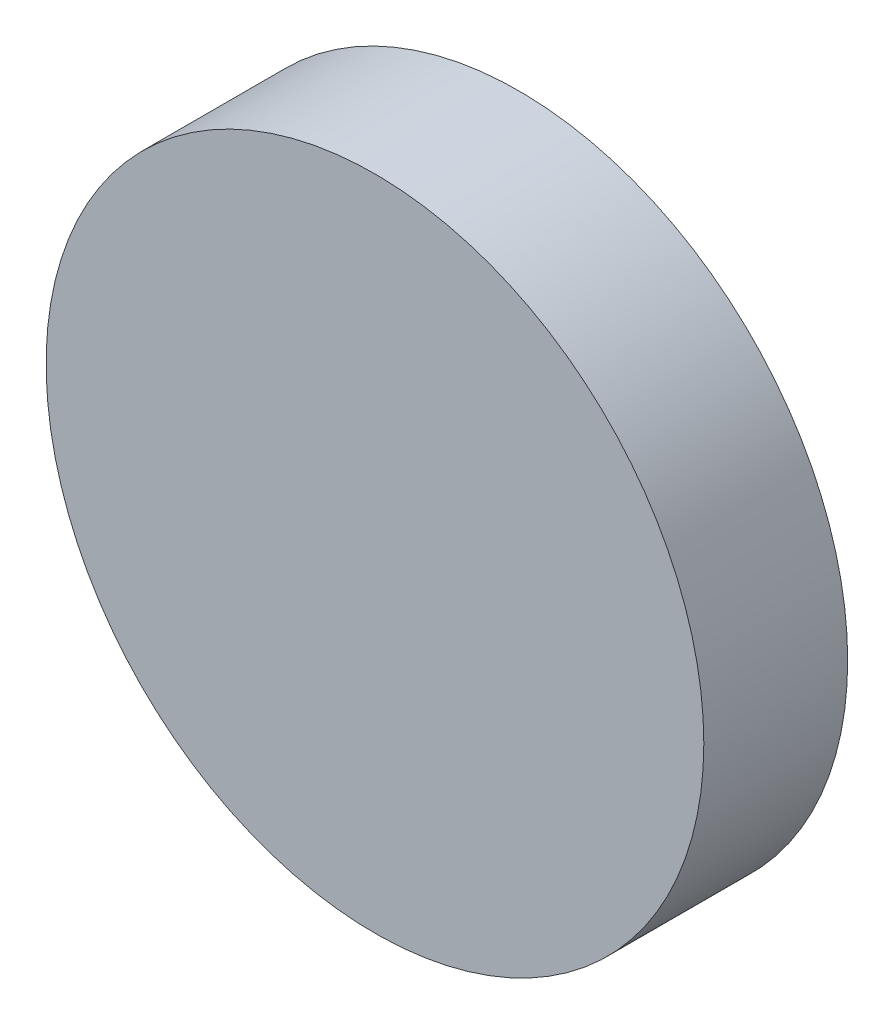
SolidWorks part; units mm, degrees
ref_plane "Alzado" through (0, 0, 0) normal (0, 0, 1) x (1, 0, 0)
ref_plane "Planta" through (0, 0, 0) normal (0, 1, 0) x (1, 0, 0)
ref_plane "Vista lateral" through (0, 0, 0) normal (1, 0, 0) x (0, 0, -1)
sketch "Croquis2" plane through (0, 0, 34) normal (0, 0, 1) x (1, 0, 0)
  circle A3 centre (13.5413, 6.6268) radius 40
  circle A6 centre (13.5413, 6.6268) radius 37.5
extrude "Saliente-Extruir1" add sketch "Croquis2" along normal blind 12
sketch "Croquis3" plane through (0, 0, 46) normal (0, 0, 1) x (1, 0, 0)
  circle A2 centre (13.5413, 6.6268) radius 40
  circle A3 centre (13.5413, 6.6268) radius 40
  circle A5 centre (13.5413, 6.6268) radius 37.5
  circle A6 centre (13.5413, 6.6268) radius 37.5
  circle A9 centre (13.5413, 6.6268) radius 35
  dimension "D1" = 0
  dimension "D2" = 0
extrude "Saliente-Extruir2" add sketch "Croquis3" along normal up to surface (3 mm away) contours A9 region at (-25.3273, 6.6268, 46) region at (13.5413, 6.6268, 46)
sketch "Croquis4" plane through (0, 0, 49) normal (0, 0, 1) x (1, 0, 0)
  circle A2 centre (13.5413, 6.6268) radius 40
  circle A3 centre (13.5413, 6.6268) radius 40
  dimension "D1" = 0
extrude "Saliente-Extruir3" add sketch "Croquis4" along normal blind 2.5
